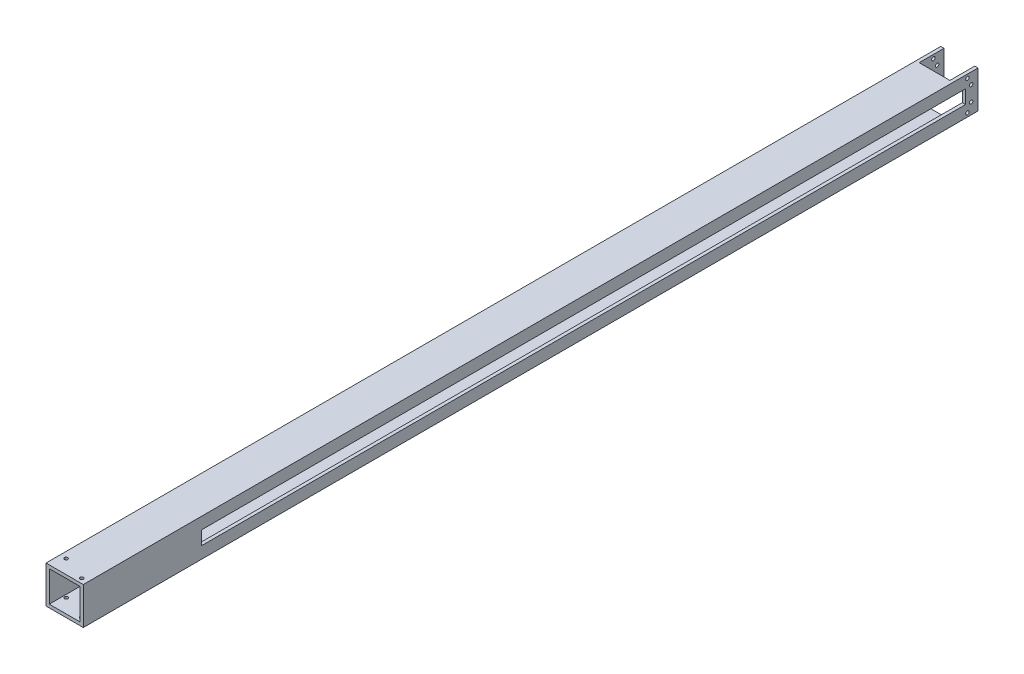
SolidWorks part; units mm, degrees
ref_plane "Front Plane" through (0, 0, 0) normal (1, 0, 0) x (0, 1, 0)
ref_plane "Top Plane" through (0, 0, 0) normal (0, 0, 1) x (0, 1, 0)
ref_plane "Right Plane" through (0, 0, 0) normal (0, 1, 0) x (-1, 0, 0)
sketch "Sketch1" plane through (0, 0, 0) normal (0, 0, 1) x (0, 1, 0)
  line L0 (19.05, -19.05) -> (19.05, 19.05)
  line L1 (19.05, -19.05) -> (-19.05, -19.05)
  line L2 (19.05, -19.05) -> (19.05, 19.05)
  line L3 (19.05, 19.05) -> (-19.05, 19.05)
  line L4 (-19.05, -19.05) -> (-19.05, 19.05)
  line L5 (19.05, -19.05) -> (-19.05, 19.05) construction
  line L6 (19.05, 19.05) -> (-19.05, -19.05) construction
  line L7 (19.05, 19.05) -> (-19.05, 19.05)
  line L8 (-19.05, -19.05) -> (-19.05, 19.05)
  line L9 (19.05, -19.05) -> (-19.05, -19.05)
  line L10 (15.7163, 15.7163) -> (-15.7162, 15.7163)
  line L11 (-15.7162, -15.7163) -> (-15.7162, 15.7163)
  line L12 (15.7163, -15.7162) -> (-15.7162, -15.7163)
  line L13 (15.7163, -15.7162) -> (15.7163, 15.7163)
  line L14 (-6.985, -15.7162) -> (-6.985, -19.05)
  line L15 (6.985, -15.7163) -> (6.985, -19.05)
  line L16 (-15.7162, -15.7163) -> (-6.985, -15.7162)
  line L17 (-6.985, -17.3831) -> (-19.05, -17.3831) construction
  line L18 (6.985, -17.3831) -> (19.05, -17.3831) construction
  point P0 (0, 0)
  dimension "D1" = 38.1
  dimension "D4" = 13.97
  dimension "D3" = 31.4325
  dimension "D2" = 0
extrude "Boss-Extrude1" add sketch "Sketch1" along normal blind 914.4 contours L4 L1 L0 L3 L13 L12 L11 L10 region at (18.5112, 13.0175, 0)
sketch "Sketch6" plane through (0, 0, 0) normal (0, 0, 1) x (0, 1, 0)
  line L1 (26.9875, -26.9875) -> (-26.9875, -26.9875) construction
  line L2 (26.9875, -26.9875) -> (26.9875, 26.9875) construction
  line L3 (26.9875, 26.9875) -> (-26.9875, 26.9875) construction
  line L4 (-26.9875, -26.9875) -> (-26.9875, 26.9875) construction
  line L5 (26.9875, -26.9875) -> (-26.9875, 26.9875) construction
  line L6 (26.9875, 26.9875) -> (-26.9875, -26.9875) construction
  line L11 (-26.9875, 25.8156) -> (-16.9875, 25.8156)
  line L12 (-26.9875, 25.8156) -> (-26.9875, 21.8156)
  line L13 (-26.9875, 21.8156) -> (-16.9875, 21.8156)
  line L14 (-16.9875, 25.8156) -> (-16.9875, 21.8156)
  line L15 (-23.4875, 25.8156) -> (-20.4875, 25.8156)
  line L16 (-23.4875, 25.8156) -> (-23.4875, -2.5726)
  line L17 (-23.4875, -2.5726) -> (-20.4875, -2.5726)
  line L18 (-20.4875, 25.8156) -> (-20.4875, -2.5726)
  point P0 (0, 0)
  point P14 (-21.9875, 25.8156)
  point P15 (-21.9875, 25.8156)
  dimension "D1" = 53.975
  dimension "D2" = 4
  dimension "D3" = 10
  dimension "D4" = 3
sketch "Sketch7" plane through (0, 0, 0) normal (0, 1, 0) x (-1, 0, 0)
  line L0 (-19.05, 914.4) -> (19.05, 914.4) construction
  line L1 (-12.7, 911.3875) -> (-12.7, 907.8875) construction
  line L2 (12.7, 900.1125) -> (-12.7, 900.1125) construction
  line L3 (12.7, 900.1125) -> (12.7, 909.6375) construction
  line L4 (12.7, 909.6375) -> (-12.7, 909.6375) construction
  line L5 (-12.7, 900.1125) -> (-12.7, 909.6375) construction
  line L6 (12.7, 900.1125) -> (-12.7, 909.6375) construction
  line L7 (12.7, 909.6375) -> (-12.7, 900.1125) construction
  line L8 (-19.05, 914.4) -> (-19.05, 0) construction
  circle A0 centre (-12.7, 909.6375) radius 1.75
  circle A1 centre (12.7, 900.1125) radius 1.75
  point P0 (0, 914.4)
  point P2 (0, 904.875)
  dimension "D2" = 3.5
  dimension "D1" = 9.525
  dimension "D3" = 4.7625
  dimension "D4" = 6.35
extrude "Cut-Extrude2" cut sketch "Sketch7" along normal blind 70.104 and the other way blind 58.42
sketch "Sketch8" plane through (0, 19.05, 0) normal (0, 1, 0) x (-1, 0, 0)
  line L0 (-19.05, 0) -> (19.05, 0) construction
  line L1 (15.7163, -25.4) -> (-15.7162, -25.4)
  line L2 (15.7163, -25.4) -> (15.7163, 25.4)
  line L3 (15.7163, 25.4) -> (-15.7162, 25.4)
  line L4 (-15.7162, -25.4) -> (-15.7162, 25.4)
  line L5 (15.7163, -25.4) -> (-15.7162, 25.4) construction
  line L6 (15.7163, 25.4) -> (-15.7162, -25.4) construction
  point P0 (0, 0)
  dimension "1.25" = 31.4325
  dimension "D2" = 25.4
extrude "Cut-Extrude3" cut sketch "Sketch8" against normal blind 71.882
ref_axis "Axis1" through (0, 0, 960.12) along (0, 0, -1)
sketch "Sketch11" plane through (19.05, 0, 0) normal (1, 0, 0) x (0, 1, 0)
  line L0 (6.985, 914.4) -> (6.985, 0) construction
  line L1 (-6.985, 0) -> (6.985, 0)
  line L2 (-6.985, 0) -> (-6.985, 12.7)
  line L3 (-6.985, 12.7) -> (6.985, 12.7)
  line L4 (6.985, 0) -> (6.985, 12.7)
  dimension "D1" = 12.7
extrude "Boss-Extrude2" add sketch "Sketch11" against normal up to surface (3.3338 mm away) up to face at (15.7162, -13.9171, 313.2667)
sketch "Sketch9" plane through (19.05, 0, 0) normal (1, 0, 0) x (0, 1, 0)
  line L0 (19.05, 0) -> (-19.05, 0) construction
  line L1 (19.05, 0) -> (-19.05, 0) construction
  line L2 (19.05, 0) -> (-19.05, 0) construction
  line L3 (19.05, 0) -> (-19.05, 0) construction
  line L4 (15.7163, 25.4) -> (19.05, 25.4) construction
  line L6 (15.7163, 25.4) -> (19.05, 25.4) construction
  line L10 (0, 0) -> (0, 6.35) construction
  circle A0 centre (-15.24, 10.795) radius 1.75
  circle A2 centre (15.24, 10.795) radius 1.75
  circle A3 centre (15.24, 10.795) radius 10.541 construction
  circle A5 centre (7.62, 6.985) radius 1.75
  circle A6 centre (-7.62, 6.985) radius 1.75
  point P12 (4.699, 10.795)
  point P15 (-15.24, 10.795)
  dimension "D2" = 3.5
  dimension "D3" = 6.35
  dimension "D5" = 21.082
  dimension "D7" = 7.62
  dimension "D1" = 0
  dimension "D4" = 15.24
  dimension "D6" = 10.795
  dimension "D8" = 3.81
extrude "Cut-Extrude4" cut sketch "Sketch9" against normal blind 68.326
sketch "Sketch12" plane through (19.05, 0, 0) normal (1, 0, 0) x (0, 1, 0)
  line L0 (19.05, 914.4) -> (19.05, 0) construction
  line L1 (-19.05, 914.4) -> (19.05, 914.4)
  line L2 (-19.05, 914.4) -> (-19.05, 793.75)
  line L3 (-19.05, 793.75) -> (19.05, 793.75)
  line L4 (19.05, 914.4) -> (19.05, 793.75)
  dimension "D1" = 781.05
extrude "Boss-Extrude3" add sketch "Sketch12" against normal up to surface (3.3338 mm away) up to face at (15.7163, -13.49, 10.795)
